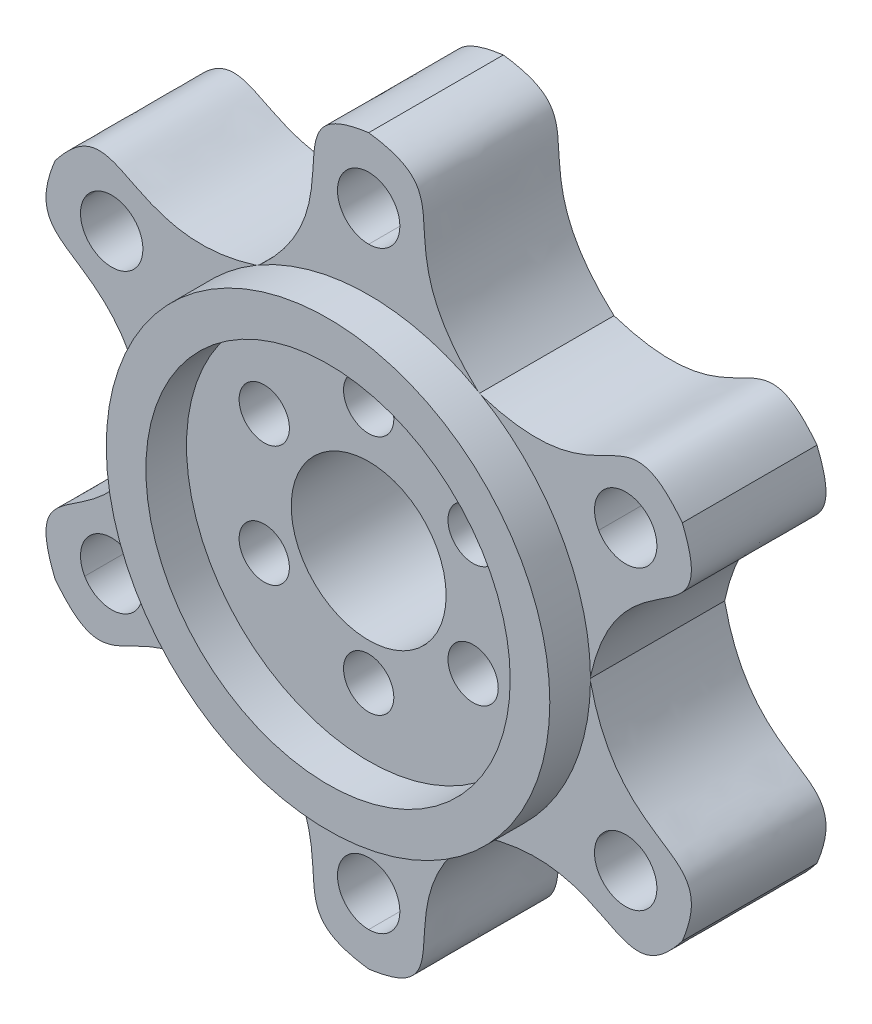
SolidWorks part; units mm, degrees
ref_plane "Front Plane" through (0, 0, 0) normal (0, 0, 1) x (1, 0, 0)
ref_plane "Top Plane" through (0, 0, 0) normal (0, 1, 0) x (1, 0, 0)
ref_plane "Right Plane" through (0, 0, 0) normal (1, 0, 0) x (0, 0, -1)
sketch "Sketch1" plane through (0, 0, 0) normal (0, 0, 1) x (1, 0, 0)
  line L0 (0, -55) -> (0, 55) construction
  line L1 (0, 0) -> (0, 45.72) construction
  circle A0 centre (0, 0) radius 9.779
  circle A1 centre (0, 0) radius 45.72
  circle A2 centre (0, 16.002) radius 3.175
  circle A3 centre (13.1849, 8.3897) radius 3.175
  circle A4 centre (13.1849, -6.8349) radius 3.175
  circle A5 centre (0, -14.4471) radius 3.175
  circle A6 centre (-13.1849, -6.8349) radius 3.175
  circle A7 centre (-13.1849, 8.3897) radius 3.175
  circle A8 centre (0, 37.465) radius 3.937
  circle A10 centre (32.4456, 18.7325) radius 3.937
  circle A11 centre (32.4456, -18.7325) radius 3.937
  circle A12 centre (0, -37.465) radius 3.937
  circle A13 centre (-32.4456, -18.7325) radius 3.937
  circle A14 centre (-32.4456, 18.7325) radius 3.937
  point P21 (0, 0.7774)
  point P36 (0, 0)
  dimension "D1" = 19.558
  dimension "D2" = 91.44
  dimension "D3" = 6.35
  dimension "D6" = 7.874
  dimension "D4" = 16.002
  dimension "D8" = 37.465
  dimension "D5" = 6
  dimension "D7" = 6
extrude "Boss-Extrude3" add sketch "Sketch1" along normal blind 17
sketch "Sketch2" plane through (0, 0, 17) normal (0, 0, 1) x (1, 0, 0)
  line L0 (0, -9.35) -> (0, 9.35) construction
  line L1 (-32.4456, 18.7325) -> (0, 37.465) construction
  line L2 (-16.2228, 28.0988) -> (-4.8895, 8.4689) construction
  line L3 (16.1678, 28.1305) -> (4.8344, 8.5004) construction
  line L6 (32.4456, -18.7325) -> (32.4456, 18.7325) construction
  line L7 (32.4456, 18.7325) -> (0, 37.465) construction
  line L8 (9.35, 0) -> (-9.35, 0) construction
  circle A0 centre (0, 0) radius 27.94 construction
  circle A1 centre (0, 0) radius 45.72 construction
  circle A2 centre (0, 0) radius 9.779 construction
  circle A3 centre (0, 0) radius 45.72
  spline S0 degree 3 poles (-13.97, 24.1967) (-0.9195, 35.9832) (-13.1193, 43.9586) (0, 45.72) knots 0 0 0 0 1 1 1 1
  spline S1 degree 3 poles (13.97, 24.1967) (0.9195, 35.9832) (13.1193, 43.9586) (0, 45.72) knots 0 0 0 0 1 1 1 1
  spline S2 degree 3 poles (-27.94, 0) (-31.6221, 17.1953) (-44.6289, 10.6177) (-39.5947, 22.86) knots 0 0 0 0 1 1 1 1
  spline S3 degree 3 poles (-13.97, 24.1967) (-30.7026, 18.7879) (-31.5096, 33.3409) (-39.5947, 22.86) knots 0 0 0 0 1 1 1 1
  spline S4 degree 3 poles (-13.97, -24.1967) (-30.7026, -18.7879) (-31.5096, -33.3409) (-39.5947, -22.86) knots 0 0 0 0 1 1 1 1
  spline S5 degree 3 poles (-27.94, 0) (-31.6221, -17.1953) (-44.6289, -10.6177) (-39.5947, -22.86) knots 0 0 0 0 1 1 1 1
  spline S6 degree 3 poles (13.97, -24.1967) (30.7026, -18.7879) (31.5096, -33.3409) (39.5947, -22.86) knots 0 0 0 0 1 1 1 1
  spline S7 degree 3 poles (27.94, 0) (31.6221, -17.1953) (44.6289, -10.6177) (39.5947, -22.86) knots 0 0 0 0 1 1 1 1
  spline S8 degree 3 poles (13.97, -24.1967) (0.9195, -35.9832) (13.1193, -43.9586) (0, -45.72) knots 0 0 0 0 1 1 1 1
  spline S9 degree 3 poles (-13.97, -24.1967) (-0.9195, -35.9832) (-13.1193, -43.9586) (0, -45.72) knots 0 0 0 0 1 1 1 1
  spline S10 degree 3 poles (27.94, 0) (31.6221, 17.1953) (44.6289, 10.6177) (39.5947, 22.86) knots 0 0 0 0 1 1 1 1
  spline S11 degree 3 poles (13.97, 24.1967) (30.7026, 18.7879) (31.5096, 33.3409) (39.5947, 22.86) knots 0 0 0 0 1 1 1 1
  point P5 (-16.2228, 28.0988)
  point P6 (16.1678, 28.1305)
  circle M8 centre (0, 0) radius 45.72
  dimension "D1" = 55.88
  dimension "D2" = 18.796
extrude "Cut-Extrude1" cut sketch "Sketch2" against normal blind 22.86 contours S1 S11 M8 | S5 S2 A3 | S10 S7 A3 | S6 S8 A3 | S9 S4 M8 | S3 S0 M8 region at (38.1245, 0, 17) region at (19.0622, 33.0168, 17) region at (19.0622, -33.0168, 17) region at (-19.0622, 33.0168, 17) region at (-19.0622, -33.0168, 17) region at (-38.1245, 0, 17)
sketch "Sketch4" plane through (0, 0, 17) normal (0, 0, 1) x (1, 0, 0)
  circle A0 centre (0, 0) radius 9.779 construction
  circle A1 centre (0, 0) radius 9.779 construction
  circle A2 centre (0, 0) radius 28
  circle A3 centre (0, 0) radius 23
  dimension "D1" = 56
  dimension "D2" = 46
extrude "Boss-Extrude4" add sketch "Sketch4" along normal blind 5.1308 contours A2 | A3
ref_plane "Plane1" through (0, 0, 0) normal (1, 0, 0) x (0, 0, -1)
ref_plane "Plane2" through (0, 0, 0) normal (-0.5, -0.866, 0) x (-0.866, 0.5, 0)
ref_plane "Plane3" through (0, 0, 0) normal (-0.5, 0.866, 0) x (0.866, 0.5, 0)
split line "Split Line1"
split line "Split Line2"
split line "Split Line3"
ref_axis "Axis1" through (0, 0, 17) along (0, 0, -1)
